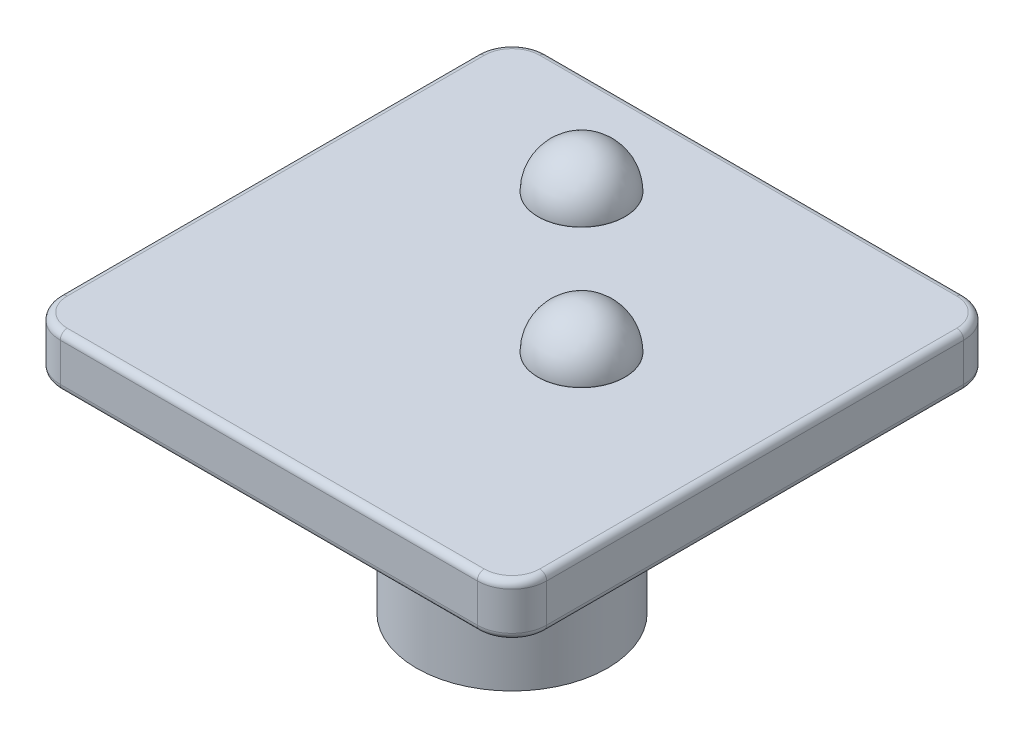
SolidWorks part; units mm, degrees
ref_plane "Front Plane" through (0, 0, 0) normal (0, 0, 1) x (1, 0, 0)
ref_plane "Top Plane" through (0, 0, 0) normal (0, 1, 0) x (1, 0, 0)
ref_plane "Right Plane" through (0, 0, 0) normal (1, 0, 0) x (0, 0, -1)
sketch "Sketch1" plane through (0, 0, 0) normal (0, 1, 0) x (1, 0, 0)
  line L1 (-7.3247, 4.3967) -> (4.6753, 4.3967)
  line L2 (-8.3247, 3.3967) -> (-8.3247, -8.6033)
  line L3 (-7.3247, -9.6033) -> (4.6753, -9.6033)
  line L4 (5.6753, 3.3967) -> (5.6753, -8.6033)
  arc A0 (-8.3247, -8.6033) -> (-7.3247, -9.6033) centre (-7.3247, -8.6033) ccw
  arc A1 (4.6753, -9.6033) -> (5.6753, -8.6033) centre (4.6753, -8.6033) ccw
  arc A2 (4.6753, 4.3967) -> (5.6753, 3.3967) centre (4.6753, 3.3967) cw
  arc A3 (-7.3247, 4.3967) -> (-8.3247, 3.3967) centre (-7.3247, 3.3967) ccw
  point P8 (5.6753, -9.6033)
  point P11 (5.6753, 4.3967)
  point P14 (-8.3247, 4.3967)
  dimension "D3" = 1
  dimension "D1" = 14
  dimension "D2" = 14
extrude "Boss-Extrude1" add sketch "Sketch1" along normal blind 1.5
sketch "Sketch2" plane through (0, 0, 0) normal (0, -1, 0) x (1, 0, 0)
  line L0 (-7.3247, 9.6033) -> (4.6753, 9.6033) construction
  line L1 (5.6753, 8.6033) -> (5.6753, -3.3967) construction
  line L2 (-1.3247, -4.3967) -> (-1.3247, 9.6033) construction
  line L3 (-8.3247, 2.6033) -> (5.6753, 2.6033) construction
  line L4 (-8.3247, -3.3967) -> (-8.3247, 8.6033) construction
  circle A0 centre (-1.3247, 2.6033) radius 2.75
  dimension "D1" = 7
  dimension "D2" = 7
extrude "Boss-Extrude2" add sketch "Sketch2" along normal blind 6
sketch "Sketch3" plane through (0, -6, 0) normal (0, -1, 0) x (1, 0, 0)
  line L0 (-1.3247, 5.3533) -> (-1.3247, -0.1467) construction
  line L1 (-3.3247, 3.1533) -> (0.6753, 3.1533)
  line L2 (-3.3247, 3.1533) -> (-3.3247, 2.0533)
  line L3 (-3.3247, 2.0533) -> (0.6753, 2.0533)
  line L4 (0.6753, 3.1533) -> (0.6753, 2.0533)
  line L5 (-1.8747, 4.6033) -> (-0.7747, 4.6033)
  line L6 (-1.8747, 4.6033) -> (-1.8747, 0.6033)
  line L7 (-1.8747, 0.6033) -> (-0.7747, 0.6033)
  line L8 (-0.7747, 4.6033) -> (-0.7747, 0.6033)
  line L9 (-4.0747, 2.6033) -> (1.4253, 2.6033) construction
  circle A3 centre (-1.3247, 2.6033) radius 2.75 construction
  circle A4 centre (-1.3247, 2.6033) radius 2.75 construction
  dimension "D7" = 0.55
  dimension "D1" = 4
  dimension "D2" = 1.1
  dimension "D3" = 1.1
  dimension "D4" = 4
  dimension "D5" = 2
  dimension "D6" = 2
  dimension "D8" = 0.55
extrude "Cut-Extrude1" cut sketch "Sketch3" against normal blind 6 contours L8 L5 L6 L1 | L1 L8 L3 L4 | L8 L1 L6 L3 | L6 L1 L2 L3 | L8 L3 L6 L7 region at (-2.5997, -6, 2.6033) region at (-1.3247, -6, 3.8783) region at (-1.3247, -6, 2.6033) region at (-0.0497, -6, 2.6033) region at (-1.3247, -6, 1.3283)
chamfer "Chamfer1" distance 0.3 angle 45 12 edges at (-1.3247, -6, 0.6033) (-1.8747, -6, 1.3283) (-2.5997, -6, 2.0533) (-3.3247, -6, 2.6033) (-2.5997, -6, 3.1533) (-0.7747, -6, 1.3283) (-0.0497, -6, 2.0533) (0.6753, -6, 2.6033) (-0.0497, -6, 3.1533) (-0.7747, -6, 3.8783) (-1.3247, -6, 4.6033) (-1.8747, -6, 3.8783)
fillet "Fillet1" radius 1 1 edges at (-1.3247, 0, -0.1467)
sketch "Sketch4" plane through (0, 1.5, 0) normal (0, 1, 0) x (1, 0, 0)
  line L0 (-1.3247, 4.3967) -> (-1.3247, -9.6033) construction
  line L1 (4.6753, 4.3967) -> (-7.3247, 4.3967) construction
  line L2 (-7.3247, -9.6033) -> (4.6753, -9.6033) construction
  line L3 (5.6753, -2.6033) -> (-8.3247, -2.6033) construction
  line L4 (-8.3247, 3.3967) -> (-8.3247, -8.6033) construction
  line L5 (5.6753, -8.6033) -> (5.6753, 3.3967) construction
  line L6 (-3.3247, 4.3967) -> (-3.3247, -9.6033) construction
  line L7 (0.6753, 4.3967) -> (0.6753, -9.6033) construction
  line L8 (-8.3247, 1.3967) -> (5.6753, 1.3967) construction
  line L9 (5.6753, -6.6033) -> (-8.3247, -6.6033) construction
  circle A0 centre (-3.3247, 1.3967) radius 1.25
  circle A1 centre (0.6753, -2.6033) radius 1.25
  dimension "D1" = 4
  dimension "D2" = 4
  dimension "D3" = 2
  dimension "D4" = 2
extrude "Boss-Extrude3" add sketch "Sketch4" along normal blind 0.01
dome "Dome1" faces to dome 1 distance 1.25 reverse direction no elliptical dome no face at (-3.3247, 1.51, -0.1467) parameters "D1"=1.25
dome "Dome4" faces to dome 1 distance 1.25 reverse direction no elliptical dome no face at (0.6753, 1.51, 3.8533) parameters "D1"=1.25
fillet "Fillet3" radius 0.2 16 edges at (5.3824, 1.5, -4.1038) (5.6753, 1.5, 2.6033) (5.3824, 1.5, 9.3104) (-1.3247, 1.5, 9.6033) (-8.0318, 1.5, 9.3104) (-8.0318, 1.5, -4.1038) (-8.3247, 1.5, 2.6033) (-1.3247, 1.5, -4.3967) (5.3824, 0, 9.3104) (5.6753, 0, 2.6033) (5.3824, 0, -4.1038) (-1.3247, 0, -4.3967) (-8.0318, 0, -4.1038) (-8.3247, 0, 2.6033) (-8.0318, 0, 9.3104) (-1.3247, 0, 9.6033)
